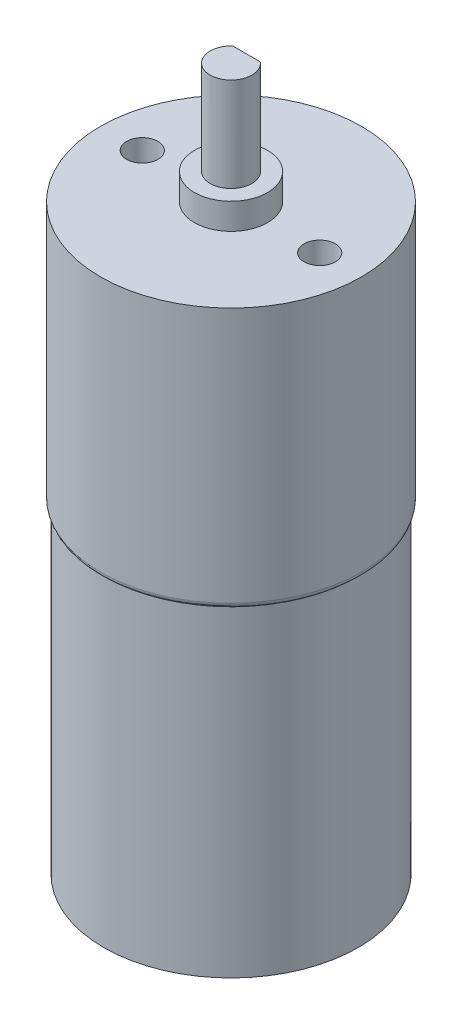
SolidWorks part; units mm, degrees
ref_plane "Front Plane" through (0, 0, 0) normal (0, 0, 1) x (1, 0, 0)
ref_plane "Top Plane" through (0, 0, 0) normal (0, 1, 0) x (1, 0, 0)
ref_plane "Right Plane" through (0, 0, 0) normal (1, 0, 0) x (0, 0, -1)
sketch "Sketch1" plane through (0, 0, 0) normal (0, 1, 0) x (1, 0, 0)
  circle A0 centre (0, 0) radius 12.5
extrude "Boss-Extrude1" add sketch "Sketch1" along normal blind 25 contours A0
fillet "Fillet1" radius 0.5 1 edges at (0, 0, 12.5) type face fillet first side face at (0, 0, 12.5) second side face at (0, 25, 12.5)
sketch "Sketch3" plane through (0, 0, 0) normal (0, -1, 0) x (1, 0, 0)
  circle A0 centre (0, 0) radius 12.2
extrude "Boss-Extrude2" add sketch "Sketch3" along normal blind 30.8
sketch "Sketch4" plane through (0, 25, 0) normal (0, 1, 0) x (1, 0, 0)
  circle A0 centre (0, 0) radius 3.5
extrude "Boss-Extrude3" add sketch "Sketch4" along normal blind 2.5
sketch "Sketch5" plane through (0, 27.5, 0) normal (0, 1, 0) x (1, 0, 0)
  circle A0 centre (0, 0) radius 2
extrude "Boss-Extrude4" add sketch "Sketch5" along normal blind 9
sketch "Sketch6" plane through (0, 36.5, 0) normal (0, 1, 0) x (1, 0, 0)
  line L0 (0, 0) -> (0, 1.5) construction
  line L1 (1.3229, 1.5) -> (-1.3229, 1.5)
  circle A1 centre (0, 0) radius 2 construction
  arc A2 (-1.3229, 1.5) -> (1.3229, 1.5) centre (0, 0) cw
  point P8 (0, 0)
extrude "Cut-Extrude1" cut sketch "Sketch6" against normal blind 8
sketch "Sketch7" plane through (0, 25, 0) normal (0, 1, 0) x (1, 0, 0)
  line L0 (-8.5, 0) -> (8.5, 0) construction
  circle A0 centre (-8.5, 0) radius 1.5
  circle A1 centre (8.5, 0) radius 1.5
  point P6 (0, 0)
extrude "Cut-Extrude2" cut sketch "Sketch7" against normal blind 5
